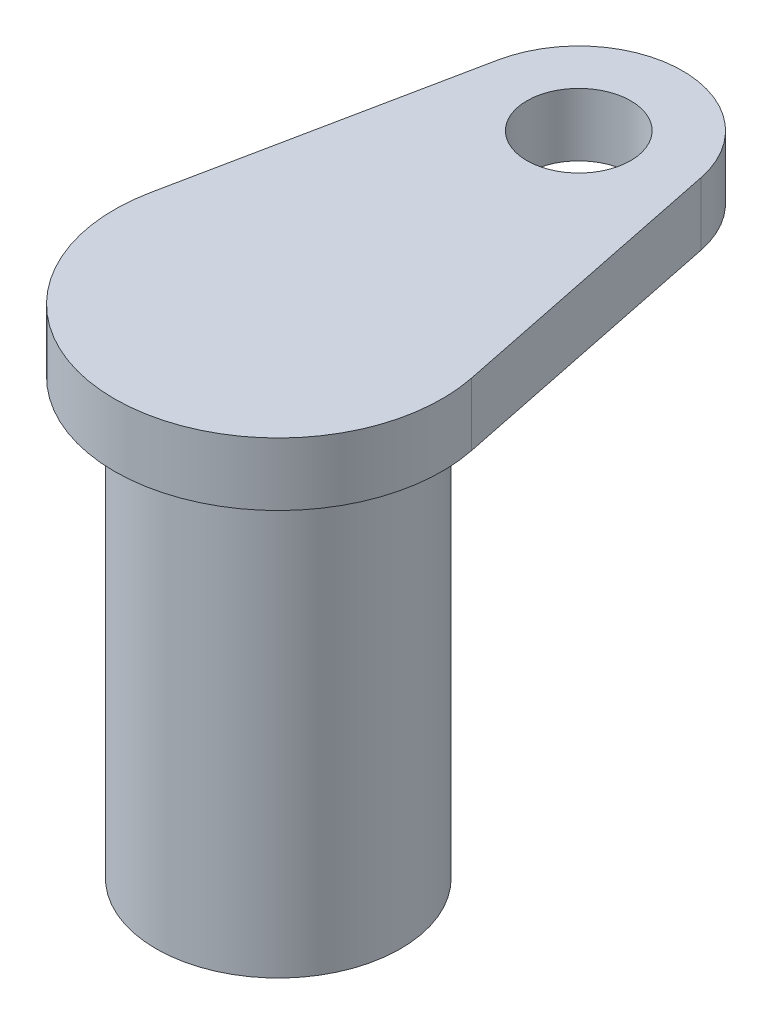
SolidWorks part; units mm, degrees
note: '?' marks a value the reader was unsure of.
material "Silicon Rubber"
ref_plane "Top" through (0, 0, 0) normal (0, 0, 1) x (1, 0, 0)
ref_plane "Right" through (0, 0, 0) normal (0, 1, 0) x (1, 0, 0)
ref_plane "Front" through (0, 0, 0) normal (1, 0, 0) x (0, 0, -1)
sketch "Sketch1" plane through (0, 0, 0) normal (0, 1, 0) x (1, 0, 0)
  line L0 (-11.7576, 2.4) -> (-7.4464, 23.52)
  line L1 (11.7576, 2.4) -> (7.4464, 23.52)
  line L2 (0, 0) -> (0, 22) construction
  arc A0 (-11.7576, 2.4) -> (11.7576, 2.4) centre (0, 0) ccw
  arc A1 (7.4464, 23.52) -> (-7.4464, 23.52) centre (0, 22) ccw
  dimension "D1" = 22
  dimension "D2" = 12
  dimension "D3" = 7.6
extrude "Base" add sketch "Sketch1" along normal blind 4.6
sketch "Sketch4" plane through (0, 0, 0) normal (0, 1, 0) x (1, 0, 0)
  circle A0 centre (0, 0) radius 8.95
  dimension "D1" = 17.9
extrude "Sensor" add sketch "Sketch4" against normal blind 31.8
hole_wizard "Bolt Hole (M7 Clearance)" positions "Sketch6" profile "Sketch5" hole size "M7" standard "ANSI Metric"
sketch "Sketch6" plane through (0, 0, 0) normal (0, -1, 0) x (-1, 0, 0)
  point P0 (0, 22)
sketch "Sketch5" plane through (0, 0, -22) normal (1, 0, 0) x (0, 0, -1)
  line L0 (0, 0) -> (0, 6.8823)
  line L1 (0, 6.8823) -> (3.8, 4.599)
  line L2 (3.8, 4.599) -> (3.8, 0)
  line L5 (3.8, 0) -> (0, 0)
  line L10 (0, 6.8823) -> (-3.8, 4.599) construction
  line L11 (0, -6.35) -> (0, 107.95) construction
  dimension "Hole Dia." = 7.6
  dimension "Hole Depth" = 4.599
  dimension "Drill Angle" = 118
ref_axis "Axis1" through (0, -31.8, 0) along (0, 1, 0)?
sketch "Sketch8" plane through (0, 0, 0) normal (1, 0, 0) x (0, 0, -1)
  line L0 (0, 0) -> (0, -58.0509)
  dimension "D1" = 58.0509
move or copy body "Body-Move/Copy1" [suppressed] bodies to move or copy 103
